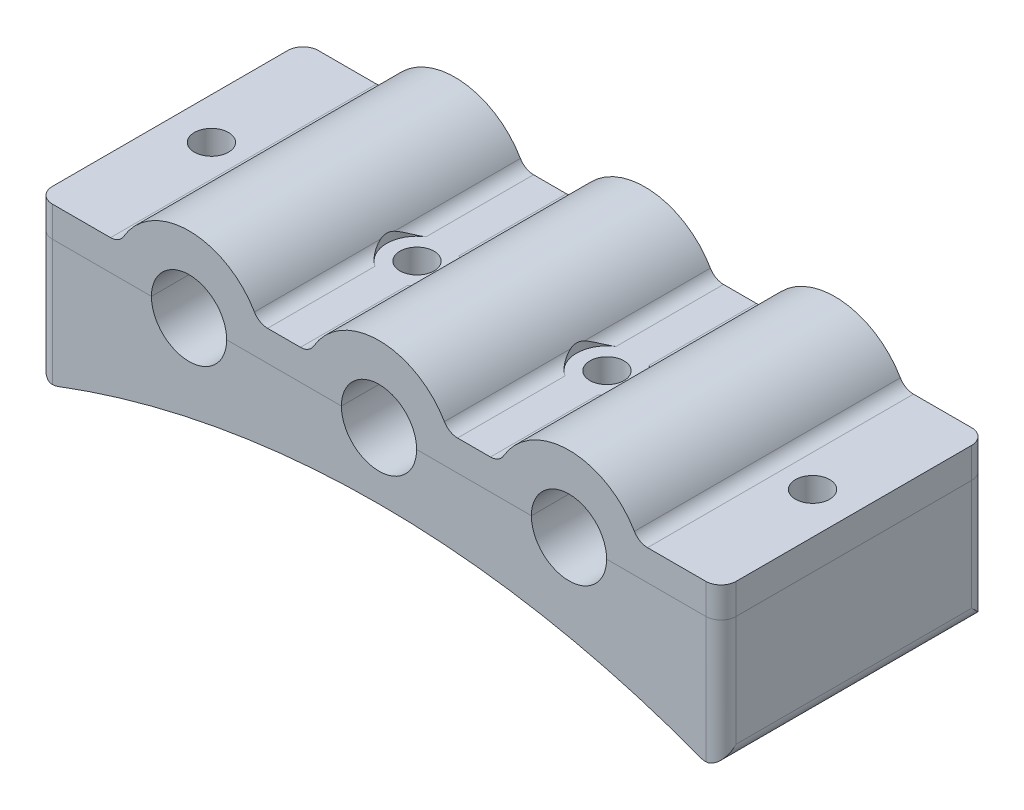
SolidWorks part; units mm, degrees
ref_plane "Front Plane" through (0, 0, 0) normal (0, 0, 1) x (1, 0, 0)
ref_plane "Top Plane" through (0, 0, 0) normal (0, 1, 0) x (1, 0, 0)
ref_plane "Right Plane" through (0, 0, 0) normal (1, 0, 0) x (0, 0, -1)
sketch "Sketch1" plane through (0, 0, 0) normal (0, 0, 1) x (1, 0, 0)
  line L0 (-25, 0) -> (25, 0) construction
  line L1 (-45, 17.5) -> (45, 17.5)
  line L2 (-45, 17.5) -> (-45, -17.5)
  line L3 (-45, -17.5) -> (45, -17.5)
  line L4 (45, 17.5) -> (45, -17.5)
  line L5 (-45, 17.5) -> (45, -17.5) construction
  line L6 (-45, -17.5) -> (45, 17.5) construction
  line L7 (-45, 0) -> (45, 0)
  line L8 (-45, 4) -> (45, 4)
  circle A0 centre (-25, 0) radius 4.85 construction
  circle A1 centre (0, 0) radius 4.85 construction
  circle A2 centre (25, 0) radius 4.85 construction
  arc A3 (-45, -17.5) -> (45, -17.5) centre (0, -128.0739) cw
  circle A4 centre (-25, 0) radius 9.95
  circle A5 centre (-25, 0) radius 4.95
  circle A6 centre (0, 0) radius 4.95
  circle A7 centre (25, 0) radius 4.95
  circle A8 centre (0, 0) radius 9.95
  circle A9 centre (25, 0) radius 9.95
  point P0 (0, 0)
  point P15 (0, 0)
  point P24 (0, -8.6939)
  point P25 (0, -4.95)
  dimension "D1" = 9.7
  dimension "D4" = 119.38
  dimension "D8" = 3.7439
  dimension "D2" = 50
  dimension "D3" = 90
  dimension "D5" = 35
  dimension "D6" = 0.1
  dimension "D7" = 4
  dimension "D9" = 5
extrude "Boss-Extrude1" add sketch "Sketch1" along normal blind 35 contours A8 L7 A4 L2 A3 | L7 A8 A3 A6 | A9 L7 A8 A3 L4 | A9 L7 L4 L8 | L7 A9 A7 | L8 A9 A7 | L7 A9 L8 A7 | L8 A9 L7 A7 | A9 L8 A8 L7 | L7 A8 L8 A6 | L8 A8 A6 | L8 A8 L7 A6 | A8 L8 A4 L7 | A5 L7 A4 L8 | A5 L8 A4 | A5 L7 A4 | A5 L8 A4 L7 | A4 L8 L2 L7
split "Split1" trim tools "Top Plane" bodies to split 101 resulting bodies 102 103
sketch "Sketch2" plane through (0, 4, 0) normal (0, 1, 0) x (1, 0, 0)
  line L0 (-45, -17.5) -> (-34.1106, -17.5) construction
  line L1 (-45, -35) -> (-45, 0) construction
  line L2 (-34.1106, -35) -> (-34.1106, 0) construction
  line L3 (-15.8894, -17.5) -> (-9.1106, -17.5) construction
  line L4 (-15.8894, -35) -> (-15.8894, 0) construction
  line L5 (-9.1106, -35) -> (-9.1106, 0) construction
  line L6 (9.1106, -17.5) -> (15.8894, -17.5) construction
  line L7 (9.1106, -35) -> (9.1106, 0) construction
  line L8 (15.8894, -35) -> (15.8894, 0) construction
  line L9 (34.1106, -17.5) -> (45, -17.5) construction
  line L10 (34.1106, -35) -> (34.1106, 0) construction
  line L11 (45, -35) -> (45, 0) construction
  circle A0 centre (-39.5553, -17.5) radius 2.25
  circle A1 centre (-12.5, -17.5) radius 2.25
  circle A2 centre (12.5, -17.5) radius 2.25
  circle A3 centre (39.5553, -17.5) radius 2.25
  circle A4 centre (-39.5553, -17.5) radius 4
  circle A5 centre (-12.5, -17.5) radius 4
  circle A6 centre (12.5, -17.5) radius 4
  circle A7 centre (39.5553, -17.5) radius 4
  point P24 (-39.5553, -17.5)
  point P25 (-12.5, -17.5)
  point P26 (12.5, -17.5)
  point P27 (39.5553, -17.5)
  dimension "D1" = 4.5
  dimension "D2" = 8
extrude "Cut-Extrude1" cut sketch "Sketch2" against normal blind 4 contours A0 | A1 | A2 | A3
sketch "Sketch4" plane through (0, 4, 0) normal (0, 1, 0) x (1, 0, 0)
  circle A1 centre (-12.5, -17.5) radius 2.25
  circle A2 centre (-12.5, -17.5) radius 2.25
  circle A3 centre (-39.5553, -17.5) radius 2.25
  circle A4 centre (-39.5553, -17.5) radius 2.25
  circle A5 centre (39.5553, -17.5) radius 4
  circle A6 centre (39.5553, -17.5) radius 4
  circle A7 centre (12.5, -17.5) radius 4
  circle A8 centre (12.5, -17.5) radius 4
  circle A9 centre (-12.5, -17.5) radius 4
  circle A10 centre (-12.5, -17.5) radius 4
  circle A11 centre (-39.5553, -17.5) radius 4
  circle A12 centre (-39.5553, -17.5) radius 4
  circle A13 centre (39.5553, -17.5) radius 2.25
  circle A14 centre (39.5553, -17.5) radius 2.25
  circle A15 centre (12.5, -17.5) radius 2.25
  circle A16 centre (12.5, -17.5) radius 2.25
  circle M9 centre (-39.5553, -17.5) radius 2.25
  dimension "D1" = 0
  dimension "D2" = 0
  dimension "D3" = 0
  dimension "D4" = 0
  dimension "D5" = 0
  dimension "D6" = 0
  dimension "D7" = 0
  dimension "D8" = 0
extrude "Cut-Extrude2" cut sketch "Sketch4" along normal through all contours A10 A2 | A8 A16 | A12 M9 | A6 A14 | M9 | A2 | A16 | A14
fillet "Fillet1" radius 2 18 edges at (-15.8894, 4, 7.688) (-16.4987, 5.1701, 17.6035) (-9.1106, 4, 7.688) (9.1106, 4, 7.688) (8.5013, 5.1701, 17.6035) (15.8894, 4, 7.688) (-8.5013, 5.1701, 17.3965) (16.4987, 5.1701, 17.3965) (45, 2, 0) (-45, 2, 0) (-34.1106, 4, 17.5) (-15.8894, 4, 27.312) (-9.1106, 4, 27.312) (9.1106, 4, 27.312) (15.8894, 4, 27.312) (34.1106, 4, 17.5) (-45, 2, 35) (45, 2, 35)
fillet "Fillet2" radius 2 6 edges at (45, -17.5, 17.5) (-45, -17.5, 17.5) (45, -8.75, 0) (45, -8.75, 35) (-45, -8.75, 0) (-45, -8.75, 35)
sketch "Sketch5" plane through (0, 0, 0) normal (0, 1, 0) x (1, 0, 0)
  circle A0 centre (-39.5553, -17.5) radius 3.025
  circle A1 centre (12.5, -17.5) radius 4
  circle A2 centre (12.5, -17.5) radius 4 construction
  circle A3 centre (39.5553, -17.5) radius 4
  circle A4 centre (39.5553, -17.5) radius 4 construction
  circle A5 centre (-39.5553, -17.5) radius 2.25
  circle A6 centre (-39.5553, -17.5) radius 2.25 construction
  circle A7 centre (-12.5, -17.5) radius 2.25
  circle A8 centre (-12.5, -17.5) radius 2.25 construction
  circle A9 centre (12.5, -17.5) radius 2.25
  circle A10 centre (12.5, -17.5) radius 2.25 construction
  circle A11 centre (39.5553, -17.5) radius 2.25
  circle A12 centre (39.5553, -17.5) radius 2.25 construction
  circle A13 centre (-39.5553, -17.5) radius 4
  circle A14 centre (-39.5553, -17.5) radius 4 construction
  circle A15 centre (-12.5, -17.5) radius 4
  circle A16 centre (-12.5, -17.5) radius 4 construction
  circle A17 centre (-12.5, -17.5) radius 3.025
  circle A18 centre (12.5, -17.5) radius 3.025
  circle A19 centre (39.5553, -17.5) radius 3.025
  dimension "D9" = 6.05
  dimension "D1" = 0
  dimension "D2" = 0
  dimension "D3" = 0
  dimension "D4" = 0
  dimension "D5" = 0
  dimension "D6" = 0
  dimension "D7" = 0
  dimension "D8" = 0
extrude "Cut-Extrude3" cut sketch "Sketch5" against normal blind 5.5
other "Save Bodies1"
